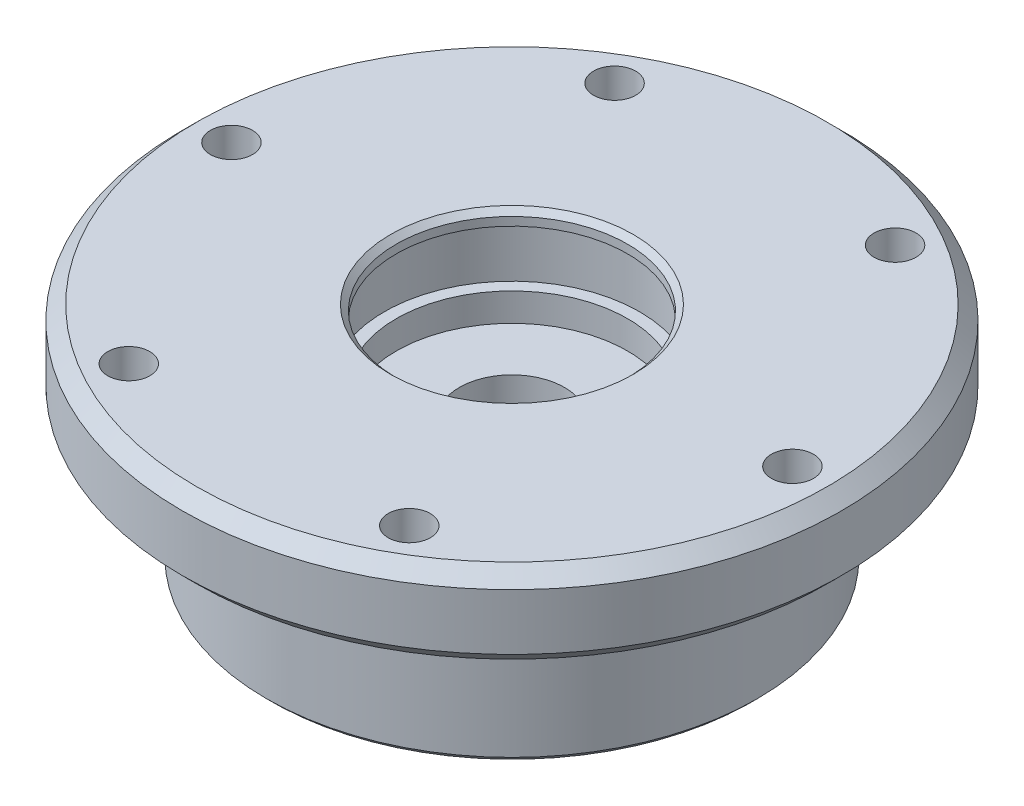
SolidWorks part; units mm, degrees
ref_plane "Front Plane" through (0, 0, 0) normal (0, 0, 1) x (1, 0, 0)
ref_plane "Top Plane" through (0, 0, 0) normal (0, 1, 0) x (1, 0, 0)
ref_plane "Right Plane" through (0, 0, 0) normal (1, 0, 0) x (0, 0, -1)
sketch "Sketch1" plane through (0, 0, 0) normal (0, 1, 0) x (1, 0, 0)
  circle A0 centre (0, 0) radius 20 construction
  circle A1 centre (20, 0) radius 1.5
  circle A2 centre (10, -17.3205) radius 1.5
  circle A3 centre (-10, -17.3205) radius 1.5
  circle A4 centre (-20, 0) radius 1.5
  circle A5 centre (-10, 17.3205) radius 1.5
  circle A6 centre (10, 17.3205) radius 1.5
  circle A7 centre (0, 0) radius 23.5
  circle A8 centre (0, 0) radius 8.25
  point P17 (0, 0)
  dimension "D1" = 40
  dimension "D2" = 3
  dimension "D5" = 16.5
  dimension "D4" = 3.5
  dimension "D3" = 6
extrude "Boss-Extrude1" add sketch "Sketch1" along normal mid plane 6
sketch "Sketch2" plane through (0, 0, 0) normal (0, 1, 0) x (1, 0, 0)
  circle A0 centre (0, 0) radius 9.1
  dimension "D1" = 18.2
extrude "Cut-Extrude1" cut sketch "Sketch2" against normal mid plane 4
sketch "Sketch3" plane through (0, -3, 0) normal (0, 1, 0) x (1, 0, 0)
  circle A0 centre (0, 0) radius 18.5
  circle A1 centre (0, 0) radius 21.5
  circle A2 centre (10, 17.3205) radius 1.5 construction
extrude "Boss-Extrude2" add sketch "Sketch3" along normal blind 1
sketch "Sketch4" plane through (0, -3, 0) normal (0, -1, 0) x (1, 0, 0)
  circle A0 centre (0, 0) radius 17.5
  circle A2 centre (0, 0) radius 3.75
  dimension "D1" = 35
  dimension "D2" = 7.5
extrude "Boss-Extrude3" add sketch "Sketch4" along normal blind 10
sketch "Sketch5" plane through (0, -3, 0) normal (0, -1, 0) x (1, 0, 0)
  circle A0 centre (0, 0) radius 19
  circle A1 centre (0, 0) radius 17.5 construction
  circle A2 centre (0, 0) radius 17.5
  dimension "D1" = 1.5
extrude "Boss-Extrude4" add sketch "Sketch5" along normal blind 0.5
chamfer "Chamfer1" distance 1 angle 45 2 edges at (0, -3, 23.5) (0, 3, 23.5)
chamfer "Chamfer2" [suppressed] distance 0.4 angle 45
chamfer "Chamfer3" distance 0.4 angle 45 1 edges at (0, 3, 8.25)
sketch "Sketch6" plane through (0, -13, 0) normal (0, -1, 0) x (1, 0, 0)
  circle A0 centre (0, 0) radius 7.5 construction
  circle A1 centre (7.5, 0) radius 2.35
  circle A2 centre (0, 7.5) radius 2.35
  circle A3 centre (-7.5, 0) radius 2.35
  circle A4 centre (0, -7.5) radius 2.35
  dimension "D1" = 15
  dimension "D2" = 4.7
extrude "Cut-Extrude2" cut sketch "Sketch6" against normal blind 4
sketch "Sketch7" plane through (0, -13, 0) normal (0, -1, 0) x (1, 0, 0)
  circle A0 centre (0, 7.5) radius 1.75
  circle A1 centre (7.5, 0) radius 1.75
  circle A2 centre (0, -7.5) radius 1.75
  circle A3 centre (-7.5, 0) radius 1.75
  dimension "D1" = 3.5
extrude "Cut-Extrude3" cut sketch "Sketch7" against normal blind 8
chamfer "Chamfer4" distance 0.4 angle 45 1 edges at (0, -13, -17.5)
sketch "Sketch8" plane through (0, -3, 0) normal (0, 1, 0) x (1, 0, 0)
  circle A0 centre (0, 0) radius 8.25 construction
  circle A1 centre (0, 0) radius 8.25
extrude "Cut-Extrude4" cut sketch "Sketch8" against normal blind 1
equation "\"RotorRadius\"= 26mm"
equation "\"Eccentricity\"= 1.00mm"
equation "\"RollerRadius\"= 1.5mm"
equation "\"GearRatio\"= 20"
equation "\"RollerCount\"=\"GearRatio\" + 1"
equation "\"RotorThickness\"= 6mm"
equation "\"OutputRollerRadius\"= 1.5mm"
equation "\"OutputRollerCount\"= 6"
equation "\"OutputRollerHoleCircleRadius\"=\"RotorRadius\"- 4 * \"OutputRollerRadius\""
equation "\"RotorGap\"= 0.5mm"
equation "\"D1@Sketch1\"=2*\"OutputRollerHoleCircleRadius\""
equation "\"D2@Sketch1\"=\"OutputRollerRadius\"*2"
equation "\"D1@Boss-Extrude1\"=\"RotorThickness\""
